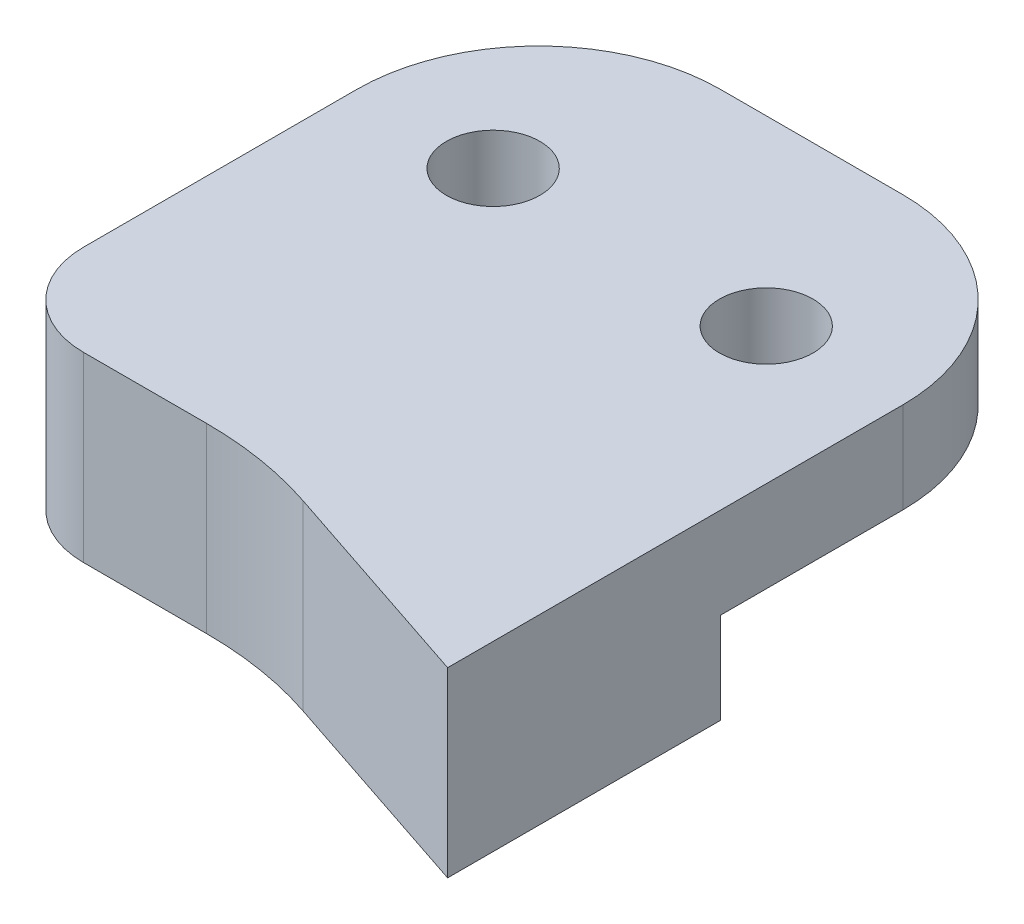
SolidWorks part; units mm, degrees
material "Alloy Steel"
ref_plane "Front Plane" through (0, 0, 0) normal (0, 0, 1) x (1, 0, 0)
ref_plane "Top Plane" through (0, 0, 0) normal (0, 1, 0) x (1, 0, 0)
ref_plane "Right Plane" through (0, 0, 0) normal (1, 0, 0) x (0, 0, -1)
sketch "Sketch1" plane through (0, 0, 0) normal (0, 1, 0) x (1, 0, 0)
  line L0 (-19.05, -6.35) -> (19.05, -6.35)
  line L2 (19.05, -19.05) -> (19.05, 19.05)
  line L3 (19.05, 19.05) -> (-19.05, 19.05)
  line L4 (-19.05, -19.05) -> (-19.05, 19.05)
  line L5 (19.05, -19.05) -> (-19.05, 19.05) construction
  line L6 (19.05, 19.05) -> (-19.05, -19.05) construction
  line L7 (0, 33.1904) -> (0, -26.0773) construction
  line L8 (3.9103, -20.3534) -> (19.05, -25.4)
  line L9 (19.05, -25.4) -> (19.05, -19.05)
  line L10 (-19.05, -19.05) -> (-4.1219, -19.05)
  circle A1 centre (-9.525, 6.35) radius 3.2639
  circle A2 centre (9.525, 6.35) radius 3.2639
  arc A5 (3.9103, -20.3534) -> (-4.1219, -19.05) centre (-4.1219, -44.45) ccw
  point P0 (0, 0)
  point P23 (0, -19.05)
  dimension "D4" = 6.5278
  dimension "D9" = 25.4
  dimension "D1" = 38.1
  dimension "D2" = 38.1
  dimension "D3" = 12.7
  dimension "D6" = 9.525
  dimension "D7" = 12.7
  dimension "D8" = 6.35
extrude "Boss-Extrude1" add sketch "Sketch1" along normal blind 6.35 contours L4 L0 L2 L3 A1 A2 | A5 L8 L9 L2 L0 L4 L10 region at (0, 0, -6.35) region at (1.4087, 0, 13.6502)
extrude "Boss-Extrude2" add sketch "Sketch1<7>" against normal blind 6.35 contours A5 L8 L9 L2 L0 L4 L10 region at (1.4087, 0, 13.6502)
sketch "Sketch1<7>" plane through (0, 0, 0) normal (0, 1, 0) x (1, 0, 0) same geometry as "Sketch1"
fillet "Fillet1" radius 6.35 1 edges at (-19.05, 0, 19.05)
fillet "Fillet2" radius 12.7 2 edges at (19.05, 3.175, -19.05) (-19.05, 3.175, -19.05)
